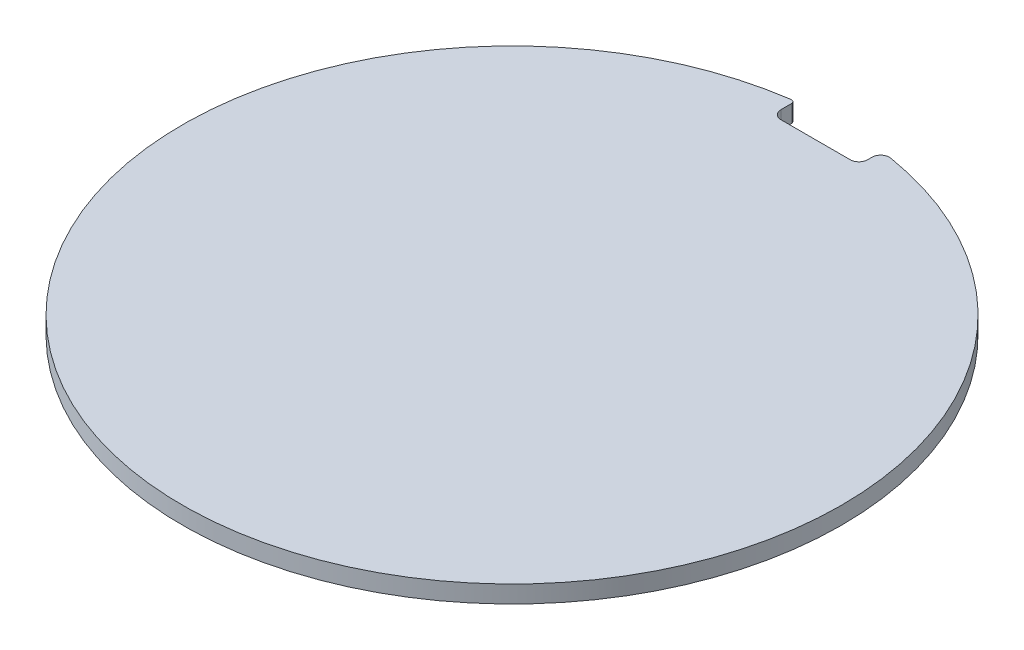
SolidWorks part; units mm, degrees
ref_plane "Front Plane" through (0, 0, 0) normal (0, 0, 1) x (1, 0, 0)
ref_plane "Top Plane" through (0, 0, 0) normal (0, 1, 0) x (1, 0, 0)
ref_plane "Right Plane" through (0, 0, 0) normal (1, 0, 0) x (0, 0, -1)
sketch "Sketch1" plane through (0, 0, 0) normal (0, 1, 0) x (1, 0, 0)
  line L0 (2.5, 18.2551) -> (2.5, 18)
  line L1 (2, 17.5) -> (-2, 17.5)
  line L2 (-2.5, 18) -> (-2.5, 18.6051)
  arc A0 (-2.7287, 18.803) -> (3.0811, 18.7485) centre (0, 0) ccw
  arc A1 (3.0811, 18.7485) -> (2.5, 18.2551) centre (3, 18.2551) ccw
  arc A2 (2.5, 18) -> (2, 17.5) centre (2, 18) cw
  arc A3 (-2, 17.5) -> (-2.5, 18) centre (-2, 18) cw
  arc A4 (-2.5, 18.6051) -> (-2.7287, 18.803) centre (-2.7, 18.6051) ccw
extrude "Boss-Extrude1" add sketch "Sketch1" along normal blind 1
ref_plane "DICHTSCHEIBE XY" through (0, 0, 0) normal (0, 1, 0) x (1, 0, 0)
ref_plane "DICHTSCHEIBE XZ" through (0, 0, 0) normal (0, 0, 1) x (1, 0, 0)
ref_plane "DICHTSCHEIBE YZ" through (0, 0, 0) normal (1, 0, 0) x (0, 0, -1)
ref_axis "DICHTSCHEIBE X" through (-80.9, 0, 0) along (1, 0, 0)
ref_axis "DICHTSCHEIBE Y" through (0, 0, 50) along (0, 0, -1)
ref_axis "DICHTSCHEIBE Z" through (0, 50, 0) along (0, -1, 0)
sketch3d "DICHTSCHEIBE"
  point P0 (0, 0, 0)
other "Freeze***"
